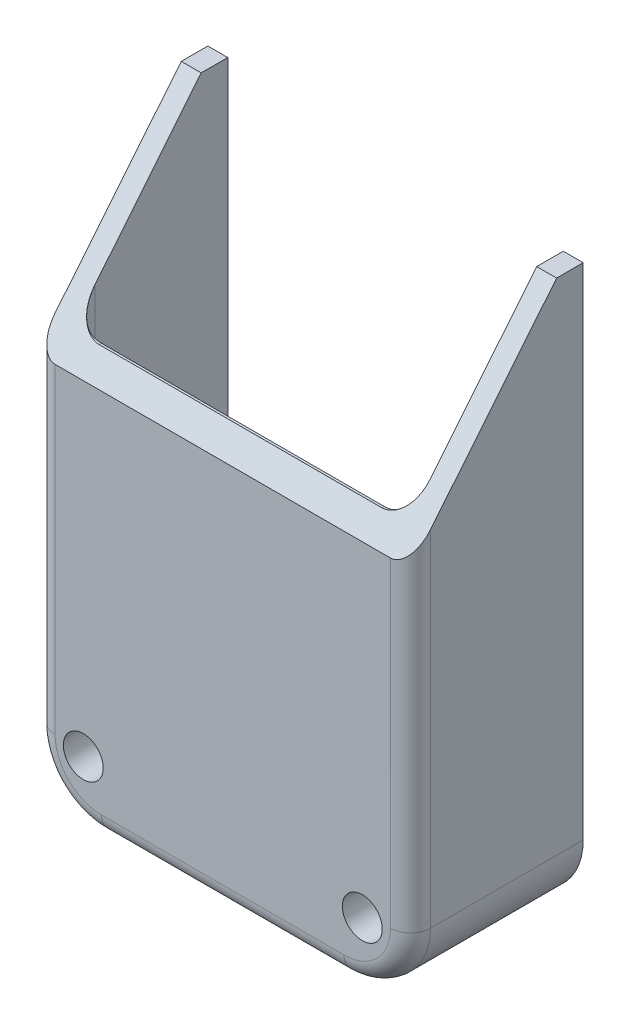
SolidWorks part; units mm, degrees
material "ABS"
ref_plane "Plano frontal" through (0, 0, 0) normal (0, 0, 1) x (1, 0, 0)
ref_plane "Plano superior" through (0, 0, 0) normal (0, 1, 0) x (1, 0, 0)
ref_plane "Plano direito" through (0, 0, 0) normal (1, 0, 0) x (0, 0, -1)
sketch "Esboço1" plane through (0, 0, 0) normal (0, 0, 1) x (1, 0, 0)
  line L1 (-28.25, -35.5) -> (28.25, -35.5)
  line L2 (-28.25, -35.5) -> (-28.25, 49.75)
  line L3 (-28.25, 49.75) -> (28.25, 49.75)
  line L4 (28.25, -35.5) -> (28.25, 49.75)
  point P0 (0, 0)
  dimension "D1" = 56.5
  dimension "D2" = 49.75
  dimension "D3" = 35.5
  dimension "D4" = 28.25
extrude "Ressalto-extrusão1" add sketch "Esboço1" along normal blind 26
fillet "Filete1" radius 10 2 edges at (-28.25, -35.5, 13) (28.25, -35.5, 13)
chamfer "Chanfro1" distance 22 distance2 27 1 edges at (0, 49.75, 26) first distance on face at (0, 49.75, 13)
fillet "Filete2" radius 3 5 edges at (28.25, -1.375, 26) (25.3211, -32.5711, 26) (0, -35.5, 26) (-25.3211, -32.5711, 26) (-28.25, -1.375, 26)
shell "Casca1" thickness 3 removed face at (0, -4.4404, 0)
sketch "Esboço2" plane through (0, 0, 26) normal (0, 0, 1) x (1, 0, 0)
  line L1 (-25.25, 49.75) -> (25.25, 49.75)
  line L2 (-25.25, 49.75) -> (-25.25, 26)
  line L3 (-25.25, 26) -> (25.25, 26)
  line L4 (25.25, 49.75) -> (25.25, 26)
  line L5 (28.25, 26.4318) -> (28.25, -25.5) construction
  line L6 (-28.25, -25.5) -> (-28.25, 26.4318) construction
  line L7 (25.25, 49.75) -> (-25.25, 49.75) construction
  dimension "D1" = 26
  dimension "D2" = 0
  dimension "D3" = 3
  dimension "D4" = 3
extrude "Corte-extrusão1" cut sketch "Esboço2" against normal through all
fillet "Filete3" radius 4 2 edges at (25.25, 26, 21.417) (-25.25, 26, 21.417)
sketch "Esboço3" plane through (0, 0, 23) normal (0, 0, -1) x (-1, 0, 0)
  line L0 (0, 0) -> (0, -35.5) construction
  line L1 (18.25, -35.5) -> (-18.25, -35.5) construction
  circle A0 centre (-21, -26.25) radius 3
  circle A1 centre (21, -26.25) radius 3
  dimension "D1" = 21
  dimension "D2" = 26.25
  dimension "D3" = 6
extrude "Ressalto-extrusão2" add sketch "Esboço3" along normal blind 12
sketch "Esboço4" plane through (0, 0, 11) normal (0, 0, -1) x (-1, 0, 0)
  line L0 (0, 26) -> (0, -35.5) construction
  line L1 (-21.25, 26) -> (21.25, 26) construction
  line L2 (18.25, -35.5) -> (-18.25, -35.5) construction
  circle A0 centre (-21, -26.25) radius 1.75
  circle A1 centre (21, -26.25) radius 1.75
  dimension "D1" = 3.5
extrude "Corte-extrusão2" cut sketch "Esboço4" against normal through all
sketch "Esboço6" plane through (0, 0, 23) normal (0, 0, -1) x (-1, 0, 0)
  line L0 (-21, -21.25) -> (-25.25, -21.25)
  line L1 (-25.25, -25.5) -> (-25.25, 49.75) construction
  line L2 (-25.25, -21.25) -> (-25.25, -31.25)
  line L3 (-25.25, -31.25) -> (-21, -31.25)
  line L4 (0, 0) -> (0, -35.5) construction
  line L5 (18.25, -35.5) -> (-18.25, -35.5) construction
  line L6 (25.25, -31.25) -> (21, -31.25)
  line L7 (25.25, -21.25) -> (25.25, -31.25)
  line L8 (21, -21.25) -> (25.25, -21.25)
  circle A0 centre (-21, -26.25) radius 1.75
  arc A1 (-21, -31.25) -> (-21, -21.25) centre (-21, -26.25) ccw
  arc A2 (21, -31.25) -> (21, -21.25) centre (21, -26.25) cw
  circle A3 centre (21, -26.25) radius 1.75
  dimension "D1" = 10
extrude "Ressalto-extrusão3" add sketch "Esboço6" along normal blind 8
sketch "Esboço8" plane through (0, 0, 26) normal (0, 0, 1) x (1, 0, 0)
  line L0 (0, 0) -> (0, -35.5) construction
  line L1 (18.25, -35.5) -> (-18.25, -35.5) construction
  circle A0 centre (-21, -26.25) radius 3
  circle A1 centre (21, -26.25) radius 3
  dimension "D1" = 6
extrude "Corte-extrusão3" cut sketch "Esboço8" against normal offset from surface (9 mm away) 2 up to face at (-18, -26.25, 15)
chamfer "Chanfro2" distance 1 distance2 4 1 edges at (18, -26.25, 15) first distance on face at (18, -26.25, 15)
chamfer "Chanfro3" distance 4 distance2 1 1 edges at (-18, -26.25, 15) first distance on face at (-18, -26.25, 11)
fillet "Filete5" radius 3 5 edges at (20.3417, -32.1802, 23) (-20.3417, -32.1802, 23) (-25.25, 0.2163, 23) (0, -32.5, 23) (25.25, 0.2163, 23)
sketch "Esboço10" plane through (0, -32.5, 0) normal (0, 1, 0) x (1, 0, 0)
  line L0 (0, -26) -> (0, 0) construction
  line L8 (25.25, -26) -> (-25.25, -26) construction
  line L9 (-25.25, -20) -> (-25.25, -12.0463)
  line L10 (-25.25, -4) -> (-25.25, -20.0926) construction
  line L11 (-25.25, -12.0463) -> (25.25, -12.0463)
  line L12 (-22.25, -23) -> (22.25, -23)
  line L13 (22.25, -23) -> (-22.25, -23) construction
  line L14 (25.25, -20) -> (25.25, -12.0463)
  arc A2 (-22.25, -23) -> (-25.25, -20) centre (-22.25, -20) cw
  arc A3 (22.25, -23) -> (25.25, -20) centre (22.25, -20) ccw
  point P23 (0, -23)
  point P24 (0, -12.0463)
extrude "Corte-extrusão4" cut sketch "Esboço10" along normal through all from offset 50
